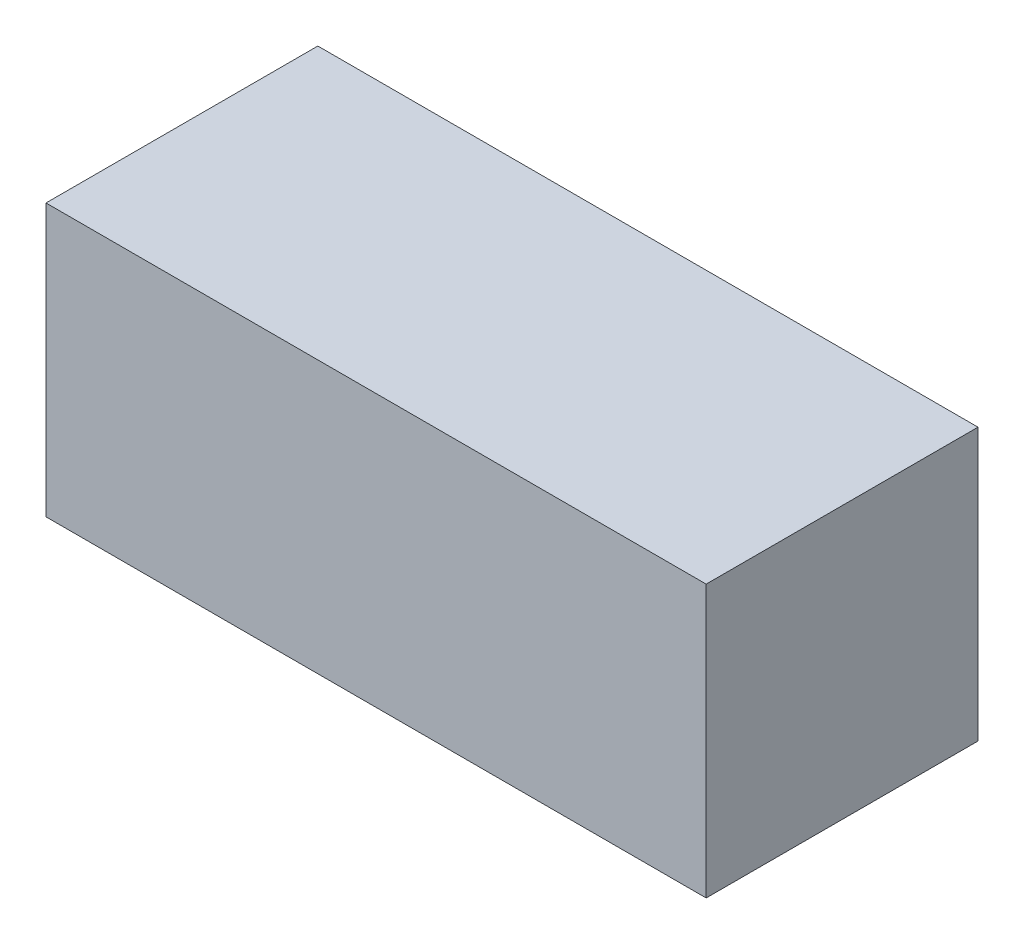
SolidWorks part; units mm, degrees
ref_plane "Front Plane" through (0, 0, 0) normal (0, 0, 1) x (1, 0, 0)
ref_plane "Top Plane" through (0, 0, 0) normal (0, 1, 0) x (1, 0, 0)
ref_plane "Right Plane" through (0, 0, 0) normal (1, 0, 0) x (0, 0, -1)
sketch "Sketch1" plane through (0, 0, 0) normal (0, 1, 0) x (1, 0, 0)
  line L1 (-85, -35) -> (85, -35)
  line L2 (-85, -35) -> (-85, 35)
  line L3 (-85, 35) -> (85, 35)
  line L4 (85, -35) -> (85, 35)
  line L5 (-85, -35) -> (85, 35) construction
  line L6 (-85, 35) -> (85, -35) construction
  point P0 (0, 0)
  dimension "D1" = 170
  dimension "D2" = 70
extrude "Boss-Extrude1" add sketch "Sketch1" along normal blind 70
equation "\"TrackerMass\"= 100'judges tracker mass"
equation "\"CargoMass\"= 250'mass of cargo"
